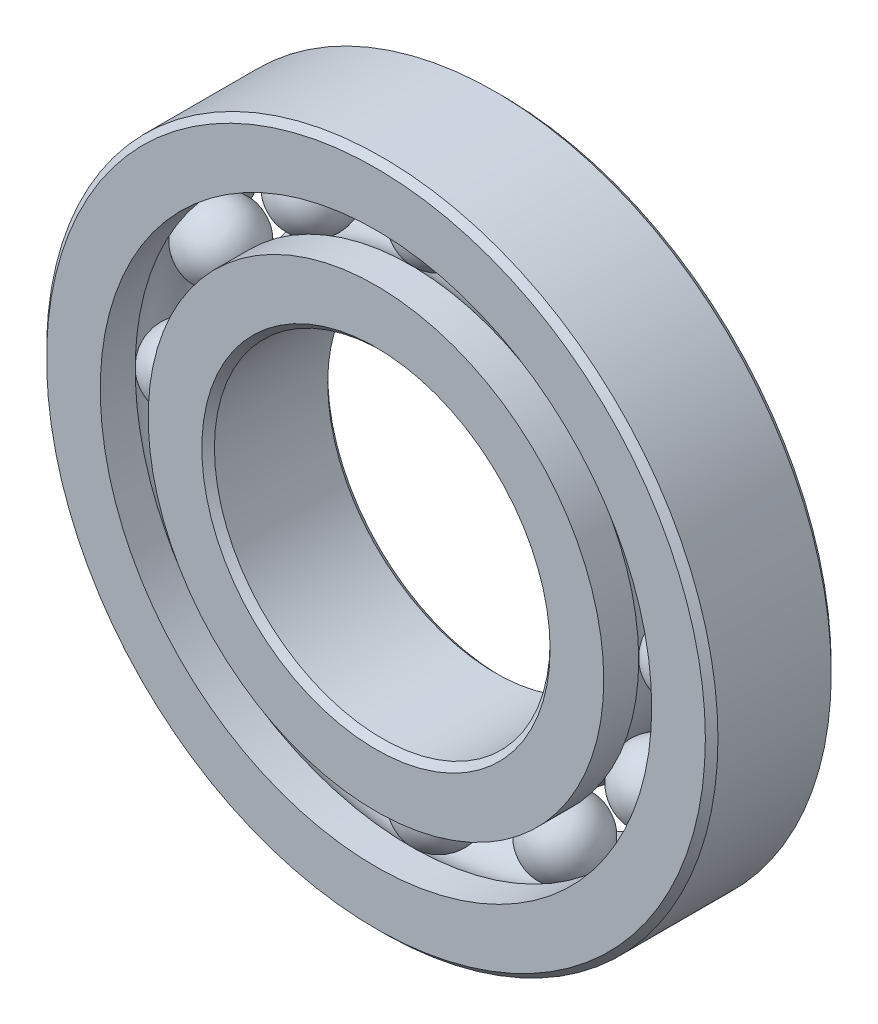
SolidWorks part; units mm, degrees
ref_plane "Front Plane" through (0, 0, 0) normal (0, 0, 1) x (1, 0, 0)
ref_plane "Top Plane" through (0, 0, 0) normal (0, 1, 0) x (1, 0, 0)
ref_plane "Right Plane" through (0, 0, 0) normal (1, 0, 0) x (0, 0, -1)
sketch "Sketch1" plane through (0, 0, 0) normal (1, 0, 0) x (0, 0, -1)
  line L0 (-4.7625, 0) -> (4.7625, 0) construction
  line L1 (0, 25.4) -> (0, -25.4) construction
  line L2 (4.2862, 25.4) -> (-4.2863, 25.4)
  line L3 (-4.2863, 25.4) -> (-4.7625, 24.9238)
  line L4 (-4.7625, 24.9238) -> (-4.7625, 20.8643)
  line L5 (-4.7625, 20.8643) -> (-2.1167, 20.8643)
  line L6 (4.7625, 20.8643) -> (2.1167, 20.8643)
  line L7 (4.7625, 24.9238) -> (4.7625, 20.8643)
  line L8 (4.2862, 25.4) -> (4.7625, 24.9238)
  line L9 (0, 25.4) -> (0, 19.05) construction
  line L10 (0, 19.05) -> (0, 12.7) construction
  arc A0 (-2.1167, 20.8643) -> (2.1167, 20.8643) centre (0, 19.05) cw
  point P14 (0, 12.7)
  dimension "D3" = 4.2333
  dimension "D1" = 45
  dimension "Width" = 9.525
  dimension "OD" = 50.8
  dimension "D2" = 0.4763
  dimension "Shaft Dia" = 25.4
  dimension "D4" = 1.8143
revolve "Revolve1" add sketch "Sketch1" angle 360 about L0
sketch "Sketch3" plane through (0, 0, 0) normal (1, 0, 0) x (0, 0, -1)
  line L0 (-4.7625, 17.2357) -> (-2.1167, 17.2357)
  line L1 (0, 25.4) -> (0, -25.4) construction
  line L2 (-4.7625, 24.9238) -> (-4.7625, 20.8643) construction
  line L3 (-4.7625, 17.2357) -> (-4.7625, 13.1762)
  line L4 (-4.2863, 25.4) -> (-4.7625, 24.9238) construction
  line L5 (-4.7625, 13.1762) -> (-4.2863, 12.7)
  line L6 (-4.2863, 12.7) -> (4.2862, 12.7)
  line L7 (4.2862, 25.4) -> (4.2862, -25.4) construction
  line L8 (4.2862, 12.7) -> (4.7625, 13.1762)
  line L9 (4.7625, -24.9238) -> (4.7625, 24.9238) construction
  line L10 (4.7625, 13.1762) -> (4.7625, 17.2357)
  line L11 (4.7625, 17.2357) -> (2.1167, 17.2357)
  line L13 (4.2862, 25.4) -> (4.7625, 24.9238) construction
  arc A0 (2.1167, 20.8643) -> (-2.1167, 20.8643) centre (0, 19.05) ccw construction
  arc A1 (2.1167, 17.2357) -> (-2.1167, 17.2357) centre (0, 19.05) cw
revolve "Revolve3" add sketch "Sketch3" angle 360 about L0
sketch "Sketch4" plane through (0, 0, 0) normal (1, 0, 0) x (0, 0, -1)
  line L0 (-2.7878, 19.05) -> (2.7878, 19.05)
  arc A2 (-2.7878, 19.05) -> (2.7878, 19.05) centre (0, 19.05) cw
  arc A3 (2.1167, 20.8643) -> (-2.1167, 20.8643) centre (0, 19.05) ccw construction
revolve "Revolve4" add sketch "Sketch4" angle 360 about L0
ref_axis "Axis1" through (0, 0, -4.7625) along (0, 0, 1)
pattern_circular "CirPattern1" count 12 every 30 about axis through (0, 0, -4.7625) along (0, 0, 1) of bodies 104
sketch "Sketch5" plane through (0, 0, 0) normal (1, 0, 0) x (0, 0, -1)
  line L0 (-4.7625, 20.8643) -> (-2.1167, 20.8643) construction
  line L1 (-4.5244, 20.8643) -> (-2.7878, 20.8643)
  line L2 (-4.5244, 20.8643) -> (-4.5244, 17.2357)
  line L3 (-4.5244, 17.2357) -> (-2.7878, 17.2357)
  line L4 (-2.7878, 20.8643) -> (-2.7878, 17.2357)
  line L5 (-4.7625, 17.2357) -> (-2.1167, 17.2357) construction
  line L6 (4.7625, 20.8643) -> (2.1167, 20.8643) construction
  line L7 (4.5244, 20.8643) -> (2.7878, 20.8643)
  line L8 (4.5244, 20.8643) -> (4.5244, 17.2357)
  line L9 (4.5244, 17.2357) -> (2.7878, 17.2357)
  line L10 (2.7878, 20.8643) -> (2.7878, 17.2357)
  line L11 (4.7625, 17.2357) -> (2.1167, 17.2357) construction
  line L12 (-4.2863, 25.4) -> (-4.7625, 24.9238) construction
  point P18 (-4.5244, 25.1619)
revolve "Revolve5" [suppressed] add sketch "Sketch5" angle 360 about L0
equation "\"D2@Sketch1\" = \"Width@Sketch1\"*.05"
equation "\"D3@Sketch1\" = \"Width@Sketch1\"/2.25"
equation "\"D4@Sketch1\" = (((\"OD@Sketch1\"-\"Width@Sketch1\")/2)/3.25)/3.5"
equation "\"D2@CirPattern1\" = 360/\"Balls@CirPattern1\""
